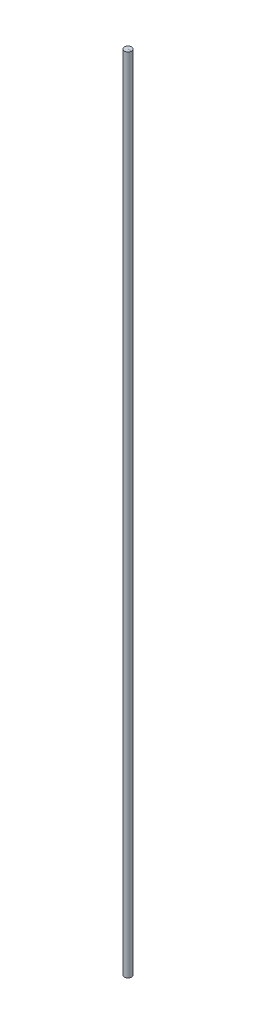
SolidWorks part; units mm, degrees
ref_plane "Front Plane" through (0, 0, 0) normal (0, 0, 1) x (1, 0, 0)
ref_plane "Top Plane" through (0, 0, 0) normal (0, 1, 0) x (1, 0, 0)
ref_plane "Right Plane" through (0, 0, 0) normal (1, 0, 0) x (0, 0, -1)
sketch "Sketch1" plane through (0, 0, 0) normal (0, 1, 0) x (1, 0, 0)
  line L0 (0, 0) -> (2, 0) construction
  circle A0 centre (0, 0) radius 2
  point P4 (0, 0)
  dimension "D1" = 4
extrude "Boss-Extrude1" add sketch "Sketch1" along normal blind 440
sketch "Sketch2" plane through (0, 440, 0) normal (0, 1, 0) x (1, 0, 0)
  line L0 (0, 0) -> (2, 0)
  line L1 (0, 0) -> (0, -0.1614)
  line L2 (0, -0.1614) -> (2, 0)
  circle A0 centre (0, 0) radius 2 construction
  point P0 (0, 0)
extrude "Boss-Extrude2" add sketch "Sketch2" along normal blind 0.0254
ref_plane "Plane1" through (0, 220, 0) normal (0, 1, 0) x (1, 0, 0)
mirror "Mirror1" about plane through (0, 220, 0) normal (0, 1, 0) of "Boss-Extrude2"
ref_axis "Axis1" through (0, 603.7779, 0) along (0, -1, 0)
